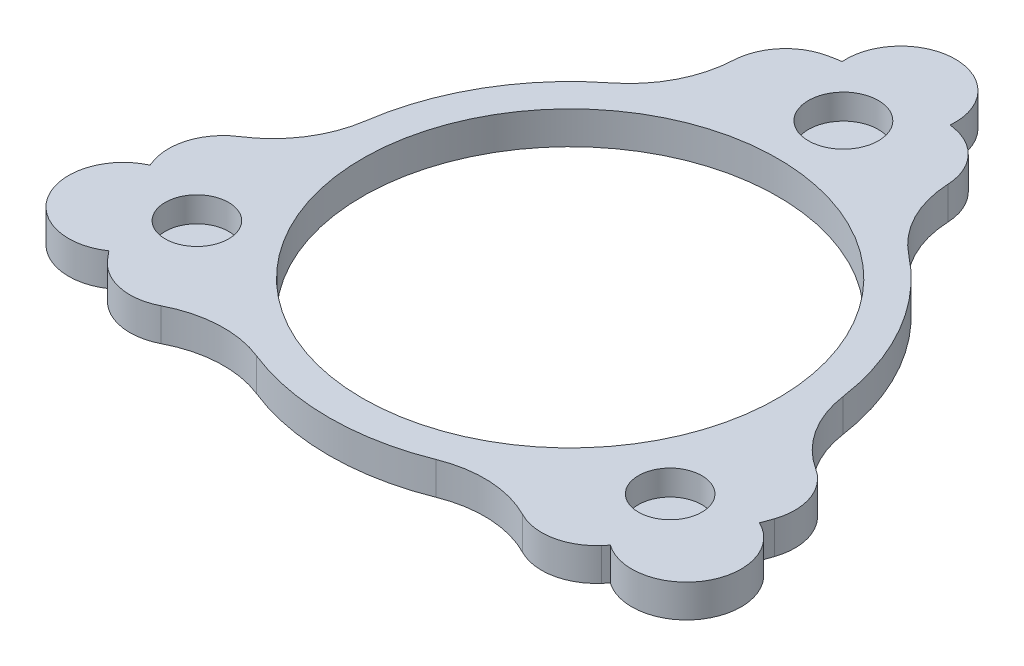
SolidWorks part; units mm, degrees
ref_plane "Спереди" through (0, 0, 0) normal (0, 0, 1) x (1, 0, 0)
ref_plane "Сверху" through (0, 0, 0) normal (0, 1, 0) x (1, 0, 0)
ref_plane "Справа" through (0, 0, 0) normal (1, 0, 0) x (0, 0, -1)
sketch "Sketch1" plane through (0, 0, 0) normal (0, 1, 0) x (1, 0, 0)
  circle A0 centre (0, 0) radius 19
  dimension "D1" = 38
extrude "Boss-Extrude1" add sketch "Sketch1" along normal blind 3.5
sketch "Sketch2" plane through (0, 0, 0) normal (0, 1, 0) x (1, 0, 0)
  circle A0 centre (0, 0) radius 30
  circle A1 centre (0, 0) radius 19
  circle A2 centre (0, 0) radius 25 construction
  circle A3 centre (0, 25) radius 2.8
  circle A4 centre (21.6506, -12.5) radius 2.8
  circle A5 centre (-21.6506, -12.5) radius 2.8
  point P16 (0, 0)
  dimension "D2" = 50
  dimension "D1" = 3
extrude "Boss-Extrude2" add sketch "Sketch2" along normal blind 3
sketch "Sketch4" plane through (0, 0, 0) normal (0, -1, 0) x (1, 0, 0)
  circle A0 centre (-21.6506, 12.5) radius 2.9
  circle A1 centre (21.6506, 12.5) radius 2.9
  circle A2 centre (0, -25) radius 2.9
  point P9 (0, 0)
  dimension "D1" = 3
extrude "Boss-Extrude3" add sketch "Sketch4" along normal blind 2 and the other way blind 3
sketch "Sketch5" plane through (0, 3, 0) normal (0, 1, 0) x (1, 0, 0)
  circle A0 centre (-26.1031, -14.7861) radius 5
  circle A1 centre (0, 0) radius 30 construction
  circle A2 centre (0.2465, 29.999) radius 5
  circle A3 centre (25.8567, -15.2129) radius 5
  point P10 (0, 0)
  dimension "D1" = 3
extrude "Boss-Extrude4" add sketch "Sketch5" against normal blind 3
sketch "Sketch3" plane through (0, 3.5, 0) normal (0, 1, 0) x (1, 0, 0)
  circle A0 centre (0, 0) radius 19
extrude "Cut-Extrude1" cut sketch "Sketch3" against normal blind 10
sketch "Sketch6" plane through (0, 3, 0) normal (0, 1, 0) x (1, 0, 0)
  circle A0 centre (0, 25) radius 3.2
  circle A1 centre (21.6506, -12.5) radius 2.9
  circle A2 centre (-21.6506, -12.5) radius 2.9
extrude "Cut-Extrude2" cut sketch "Sketch6" against normal blind 2.3
sketch "Sketch7" plane through (0, 3, 0) normal (0, 1, 0) x (1, 0, 0)
  line L0 (0, 0) -> (-13.774, 37.8437)
  line L1 (0, 0) -> (-43.9393, -7.7477)
  line L2 (-13.774, 37.8437) -> (-43.9393, -7.7477)
  line L3 (39.6606, -6.9932) -> (15.26, 41.9264)
  line L4 (0, 0) -> (15.26, 41.9264)
  line L5 (0, 0) -> (39.6606, -6.9932)
  line L6 (-25.8866, -30.8505) -> (28.6794, -34.1787)
  line L7 (0, 0) -> (28.6794, -34.1787)
  line L8 (0, 0) -> (-25.8866, -30.8505)
  circle A0 centre (0, 0) radius 22.0646
  point P12 (0, 0)
  arc M11 (-23.2848, -18.9161) -> (22.9709, -19.2961) centre (0, 0) ccw
  arc M13 (28.0242, -10.7072) -> (5.2255, 29.5414) centre (0, 0) ccw
  arc M15 (-4.7394, 29.6233) -> (-28.1963, -10.2453) centre (0, 0) ccw
  dimension "D1" = 3
extrude "Cut-Extrude3" cut sketch "Sketch7" against normal blind 13 contours L0 L2 L1 M15 | A0 L0 L1 M15 | L5 L3 L4 M13 | A0 L5 L4 M13 | L8 L6 L7 M11 | A0 L8 L7 M11 region at (-20.9182, 3, -12.0771) region at (20.9182, 3, -12.0771) region at (0, 3, 24.1542) region at (-26.4716, 3, -15.2834) region at (13.2966, 3, -34.8634) region at (23.5548, 3, 28.9381)
fillet "Fillet1" radius 10 6 edges at (-21.7294, 1.5, 3.8315) (-14.1829, 1.5, 16.9025) (14.1829, 1.5, 16.9025) (21.7294, 1.5, 3.8315) (7.5465, 1.5, -20.734) (-7.5465, 1.5, -20.734)
fillet "Fillet2" radius 5 6 edges at (-10.2606, 1.5, -28.1908) (-29.5442, 1.5, 5.2094) (-19.2836, 1.5, 22.9813) (19.2836, 1.5, 22.9813) (29.5442, 1.5, 5.2094) (10.2606, 1.5, -28.1908)
